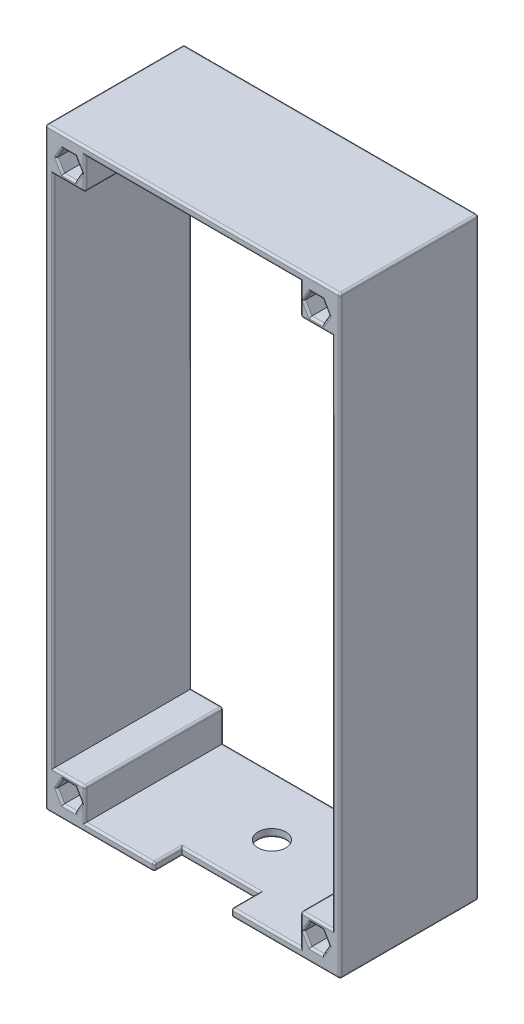
SolidWorks part; units mm, degrees
ref_plane "Front Plane" through (0, 0, 0) normal (0, 0, 1) x (1, 0, 0)
ref_plane "Top Plane" through (0, 0, 0) normal (0, 1, 0) x (1, 0, 0)
ref_plane "Right Plane" through (0, 0, 0) normal (1, 0, 0) x (0, 0, -1)
sketch "Sketch1" plane through (0, 0, 0) normal (0, 0, 1) x (1, 0, 0)
  line L0 (-35.25, -37.5) -> (-35.25, 35.5)
  line L1 (37.25, -37.5) -> (-37.25, -37.5)
  line L2 (37.25, -37.5) -> (37.25, 37.5)
  line L3 (37.25, 37.5) -> (-37.25, 37.5)
  line L4 (-37.25, -37.5) -> (-37.25, 37.5)
  line L5 (0, 37.5) -> (0, -37.5) construction
  line L6 (37.25, 0) -> (-37.25, 0) construction
  line L7 (35.25, 35.5) -> (-35.25, 35.5)
  line L8 (35.25, -37.5) -> (35.25, 35.5)
  line L9 (-31.25, 35.5) -> (-31.25, 31.5) construction
  line L10 (-31.25, 31.5) -> (-35.25, 31.5) construction
  line L11 (35.25, 31.5) -> (31.25, 31.5) construction
  line L12 (31.25, 31.5) -> (31.25, 35.5) construction
  line L13 (-31.25, 31.5) -> (-27.25, 31.5) construction
  line L14 (28.0746, 31.5) -> (29.6623, 28.75)
  line L15 (29.6623, 28.75) -> (32.8377, 28.75)
  line L16 (32.8377, 28.75) -> (34.4254, 31.5)
  line L17 (34.4254, 31.5) -> (32.8377, 34.25)
  line L18 (32.8377, 34.25) -> (29.6623, 34.25)
  line L19 (29.6623, 34.25) -> (28.0746, 31.5)
  line L20 (-28.0746, 31.5) -> (-29.6623, 34.25)
  line L21 (-29.6623, 34.25) -> (-32.8377, 34.25)
  line L22 (-32.8377, 34.25) -> (-34.4254, 31.5)
  line L23 (-34.4254, 31.5) -> (-32.8377, 28.75)
  line L24 (-32.8377, 28.75) -> (-29.6623, 28.75)
  line L25 (-29.6623, 28.75) -> (-28.0746, 31.5)
  line L26 (-31.25, 31.5) -> (-31.25, 27.5) construction
  line L27 (31.25, 31.5) -> (31.25, 27.5) construction
  line L28 (31.25, 31.5) -> (27.25, 31.5) construction
  line L29 (27.25, 31.5) -> (27.25, 35.5)
  line L30 (27.25, 31.5) -> (27.25, 27.5)
  line L31 (27.25, 27.5) -> (31.25, 27.5)
  line L32 (31.25, 27.5) -> (35.25, 27.5)
  line L33 (-31.25, 27.5) -> (-35.25, 27.5)
  line L34 (-31.25, 27.5) -> (-27.25, 27.5)
  line L35 (-27.25, 27.5) -> (-27.25, 31.5)
  line L36 (-27.25, 31.5) -> (-27.25, 35.5)
  circle A0 centre (31.25, 31.5) radius 1.75
  circle A1 centre (31.25, 31.5) radius 2.75 construction
  circle A2 centre (-31.25, 31.5) radius 1.75
  circle A3 centre (-31.25, 31.5) radius 2.75 construction
  point P0 (0, 0)
  dimension "D8" = 3.5
  dimension "D9" = 5.5
  dimension "D1" = 74.5
  dimension "D2" = 75
  dimension "D5" = 4
  dimension "D6" = 4
  dimension "D3" = 2
extrude "Boss-Extrude3" add sketch "Sketch1" along normal blind 35 contours L8 L1 L2 L3 L4 L0 L7 region at (-36.25, -36.4429, 0)
extrude "Boss-Extrude4" add sketch "Sketch1<3>" along normal up to surface (35 mm away) contours L35 L36 L7 L0 L33 L34 L25 L24 L23 L22 L21 L20 | L31 L32 L8 L7 L29 L30 L19 L18 L17 L16 L15 L14 region at (-35.1369, 31.5, 0) region at (33.25, 27.6131, 0) up to face at (0, -0.5, 35)
sketch "Sketch1<3>" plane through (0, 0, 0) normal (0, 0, 1) x (1, 0, 0) same geometry as "Sketch1"
extrude "Boss-Extrude5" add sketch "Sketch1<4>" along normal blind 29.7 contours L18 L19 L14 L15 L16 L17 A0 | L24 L25 L20 L21 L22 L23 A2 region at (28.9412, 32.833, 0) region at (-28.9412, 30.167, 0)
sketch "Sketch1<4>" plane through (0, 0, 0) normal (0, 0, 1) x (1, 0, 0) same geometry as "Sketch1"
mirror "Mirror1" about plane through (0, -37.5, 35) normal (0, -1, 0) of bodies 105
sketch "Sketch8" plane through (0, -112.5, 0) normal (0, -1, 0) x (1, 0, 0)
  line L0 (0, 35) -> (-9.75, 35)
  line L1 (37.25, 35) -> (-37.25, 35) construction
  line L2 (-9.75, 35) -> (-9.75, 28)
  line L3 (-9.75, 28) -> (9.75, 28)
  line L4 (9.75, 28) -> (9.75, 35)
  line L5 (9.75, 35) -> (0, 35)
  line L6 (0, 0) -> (0, 15) construction
  line L7 (37.25, 0) -> (-37.25, 0) construction
  circle A0 centre (0, 15) radius 3.5
  dimension "D4" = 7
  dimension "D1" = 7
  dimension "D2" = 19.5
  dimension "D3" = 15
extrude "Cut-Extrude2" cut sketch "Sketch8" against normal blind 10
fillet "Fillet2" radius 0.5 79 edges at (33, 31.5, 0) (-29.5, 31.5, 0) (37.25, -37.5, 0) (-37.25, -37.5, 0) (-35.25, -37.5, 0) (-31.25, 27.5, 0) (-27.25, 31.5, 0) (0, 35.5, 0) (27.25, 31.5, 0) (31.25, 27.5, 0) (35.25, -37.5, 0) (37.25, 37.5, 17.5) (-37.25, 37.5, 17.5) (0, 37.5, 0) (33, -106.5, 0) (-29.5, -106.5, 0) (31.25, -102.5, 0) (27.25, -106.5, 0) (0, -110.5, 0) (-27.25, -106.5, 0) (-31.25, -102.5, 0) (0, -112.5, 0) (-27.25, -102.5, 17.5) (-27.25, 27.5, 17.5) (27.25, -102.5, 17.5) (27.25, 27.5, 17.5) (37.25, -112.5, 17.5) (0, 35.5, 35) (35.25, -37.5, 35) (-35.25, -37.5, 35) (37.25, -37.5, 35) (0, 37.5, 35) (-18.5, -110.5, 35) (-37.25, -37.5, 35) (23.5, -112.5, 35) (-37.25, -112.5, 17.5) (-23.5, -112.5, 35) (-9.75, -112.5, 31.5) (0, -112.5, 28) (9.75, -112.5, 31.5) (9.75, -110.5, 31.5) (-9.75, -110.5, 31.5) (0, -110.5, 28) (27.25, -106.5, 35) (31.25, -102.5, 35) (31.25, 27.5, 35) (27.25, 31.5, 35) (-27.25, 31.5, 35) (-31.25, 27.5, 35) (-31.25, -102.5, 35) (-27.25, -106.5, 35) (-9.75, -111.5, 35) (9.75, -111.5, 35) (18.5, -110.5, 35) (-31.25, -103.75, 35) (-33.6316, -105.125, 35) (-33.6316, -107.875, 35) (-31.25, -109.25, 35) (-28.8684, -107.875, 35) (-28.8684, -105.125, 35) (31.25, -109.25, 35) (33.6316, -107.875, 35) (33.6316, -105.125, 35) (31.25, -103.75, 35) (28.8684, -105.125, 35) (28.8684, -107.875, 35) (-28.8684, 32.875, 35) (-31.25, 34.25, 35) (-33.6316, 32.875, 35) (-33.6316, 30.125, 35) (-31.25, 28.75, 35) (-28.8684, 30.125, 35) (28.8684, 30.125, 35) (31.25, 28.75, 35) (33.6316, 30.125, 35) (33.6316, 32.875, 35) (31.25, 34.25, 35) (28.8684, 32.875, 35) (0, -112.5, 11.5)
